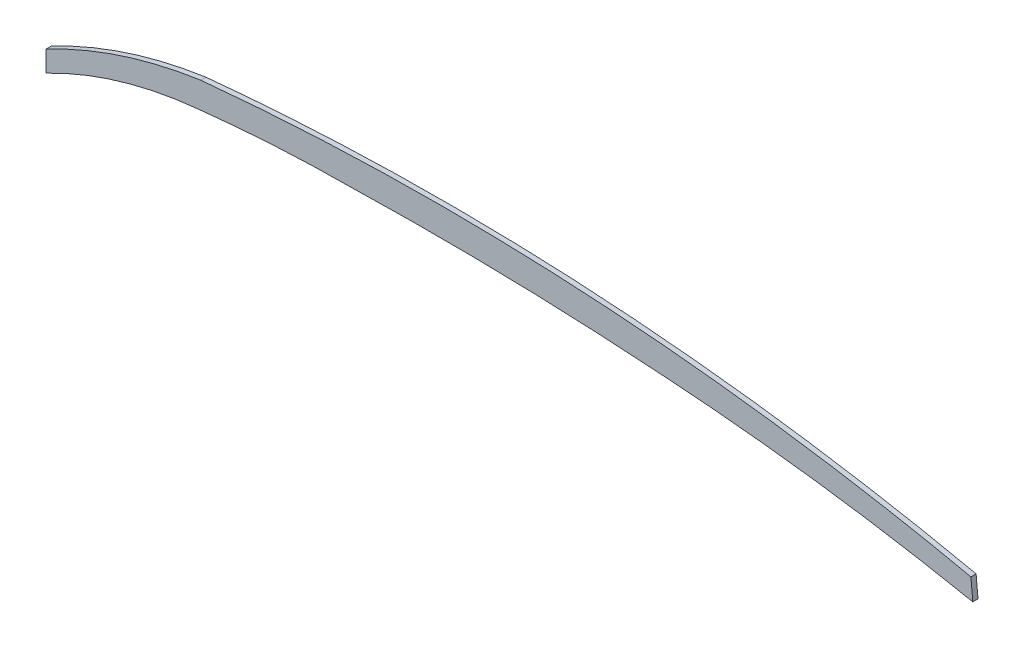
SolidWorks part; units mm, degrees
material "Balsa"
ref_plane "Front Plane" through (0, 0, 0) normal (0, 0, 1) x (1, 0, 0)
ref_plane "Top Plane" through (0, 0, 0) normal (0, 1, 0) x (1, 0, 0)
ref_plane "Right Plane" through (0, 0, 0) normal (1, 0, 0) x (0, 0, -1)
sketch "Sketch1" plane through (0, 0, 0) normal (0, 0, 1) x (1, 0, 0)
  line L0 (0, 85.9425) -> (0, 98.6503)
  line L1 (566.0852, 89.3165) -> (564.9321, 101.9675)
  arc A6 (0, 85.9425) -> (92.3925, 113.3646) centre (117.1549, -139.4255) cw
  arc A7 (92.3925, 113.3646) -> (185.8959, 118.7316) centre (190.0181, -770.2588) cw
  arc A8 (0, 98.6503) -> (94.4926, 129.4761) centre (136.5172, -159.585) cw
  arc A9 (185.8959, 118.7316) -> (373.1011, 114.6803) centre (236.8429, -1854.3326) cw
  arc A10 (373.1011, 114.6803) -> (566.0852, 89.3165) centre (283.2319, -1315.9598) cw
  spline S6 degree 3 poles (2840.1742, -3011.9753) (2207.2857, -1054.6085) (1410.1047, -9.0147) (438.4396, 123.9347) (428.6248, 125.1803) (408.999, 127.4768) (399.1847, 128.5284) (369.7378, 131.3944) (350.1011, 132.9205) (291.1746, 136.3531) (251.8686, 137.116) (-696.3591, 118.7734) (-1616.8272, -712.5738) (-2553.4552, -2680.6967) knots -5.888628 -5.888628 -5.888628 -5.888628 0.25 0.25 0.3125 0.3125 0.375 0.375 0.5 0.5 0.75 0.75 6.527741 6.527741 6.527741 6.527741 only from (564.9321, 101.9675) to (94.4926, 129.4761)
  spline S7 degree 3 poles (564.9321, 101.9675) (526.3055, 110.3591) (487.4057, 117.2349) (438.4396, 123.9347) (428.6248, 125.1803) (408.999, 127.4768) (399.1847, 128.5284) (369.7378, 131.3944) (350.1011, 132.9205) (291.1746, 136.3531) (251.8686, 137.116) (173.2133, 135.5945) (133.864, 133.3102) (94.4926, 129.4761) knots 0 0 0 0 0.25 0.25 0.3125 0.3125 0.375 0.375 0.5 0.5 0.75 0.75 1 1 1 1
  dimension "D4" = 92.3925
  dimension "D2" = 254
  dimension "D8" = 187.2051
  dimension "D9" = 28.7378
  dimension "D1" = 292.1
  dimension "D3" = 889
  dimension "D10" = 1973.7219
  dimension "D11" = 1433.46
  dimension "D5" = 27.4221
  dimension "D6" = 93.5034
  dimension "D7" = 32.7892
extrude "Boss-Extrude1" add sketch "Sketch1" against normal mid plane 3.175 contours L1 S7 A8 L0 A6 A7 A9 A10 region at (279.3924, 119.3666, 0)
equation "\"slotwidth\"=0.167708"
